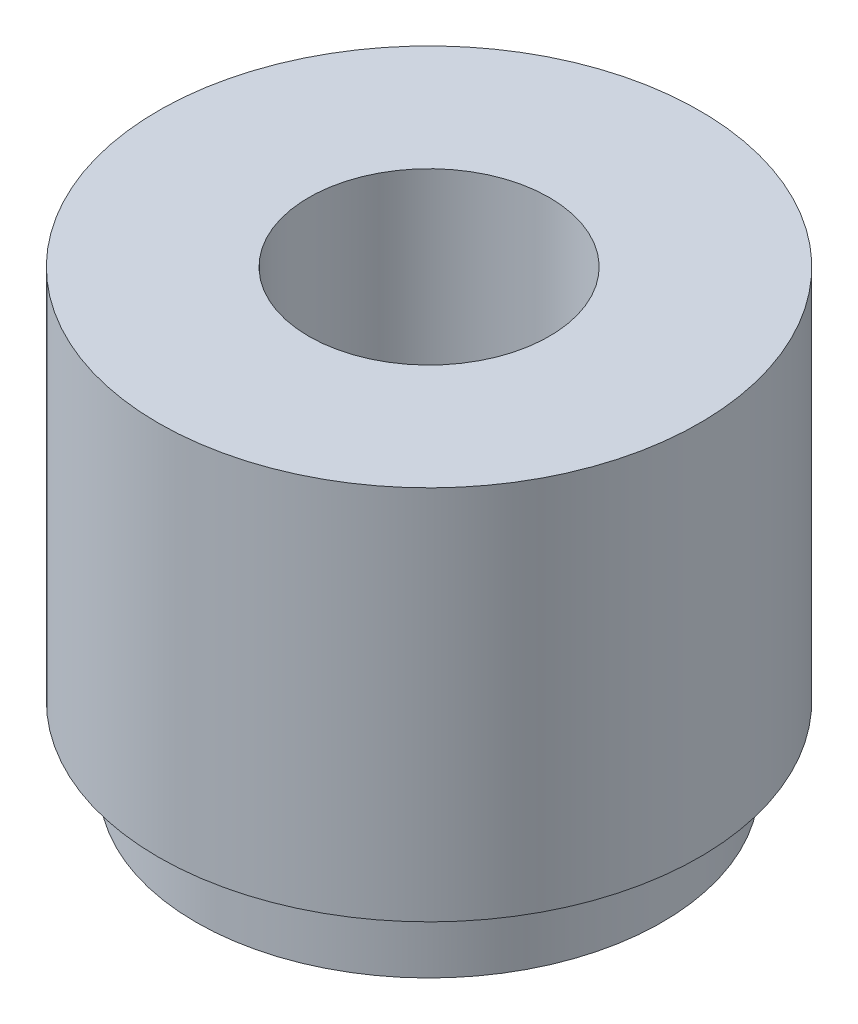
SolidWorks part; units mm, degrees
material "Brass"
ref_plane "Płaszczyzna przednia" through (0, 0, 0) normal (0, 0, 1) x (1, 0, 0)
ref_plane "Płaszczyzna górna" through (0, 0, 0) normal (0, 1, 0) x (1, 0, 0)
ref_plane "Płaszczyzna prawa" through (0, 0, 0) normal (1, 0, 0) x (0, 0, -1)
sketch "Sketch1" plane through (0, 0, 0) normal (0, 0, 1) x (1, 0, 0)
  line L0 (0, 0) -> (1.55, 0)
  line L1 (1.55, 0) -> (1.55, 0.5)
  line L2 (1.55, 0.5) -> (1.8, 0.5)
  line L3 (1.8, 0.5) -> (1.8, 3)
  line L4 (1.8, 3) -> (0, 3)
  line L5 (0, 3) -> (0, 0)
  dimension "D1" = 3
  dimension "D2" = 1.55
  dimension "D3" = 1.8
  dimension "D4" = 0.5
revolve "Revolve1" add sketch "Sketch1" angle 360 about L5
hole_wizard "Tap Drill for M2 Tap1" positions "Sketch2" profile "Sketch3" hole size "M2" standard "DIN" end condition through all
sketch "Sketch2" plane through (0, 3, 0) normal (0, 1, 0) x (1, 0, 0)
  point P0 (0, 0)
sketch "Sketch3" plane through (0, 3, 0) normal (1, 0, 0) x (0, 0, 1)
  line L0 (0, 0) -> (0, 3)
  line L1 (0, 3) -> (0.8, 3)
  line L2 (0.8, 3) -> (0.8, 0)
  line L5 (0.8, 0) -> (0, 0)
  line L11 (0, -6.35) -> (0, 107.95) construction
  dimension "Thru Hole Dia." = 1.6
  dimension "Thru Hole Depth" = 3
